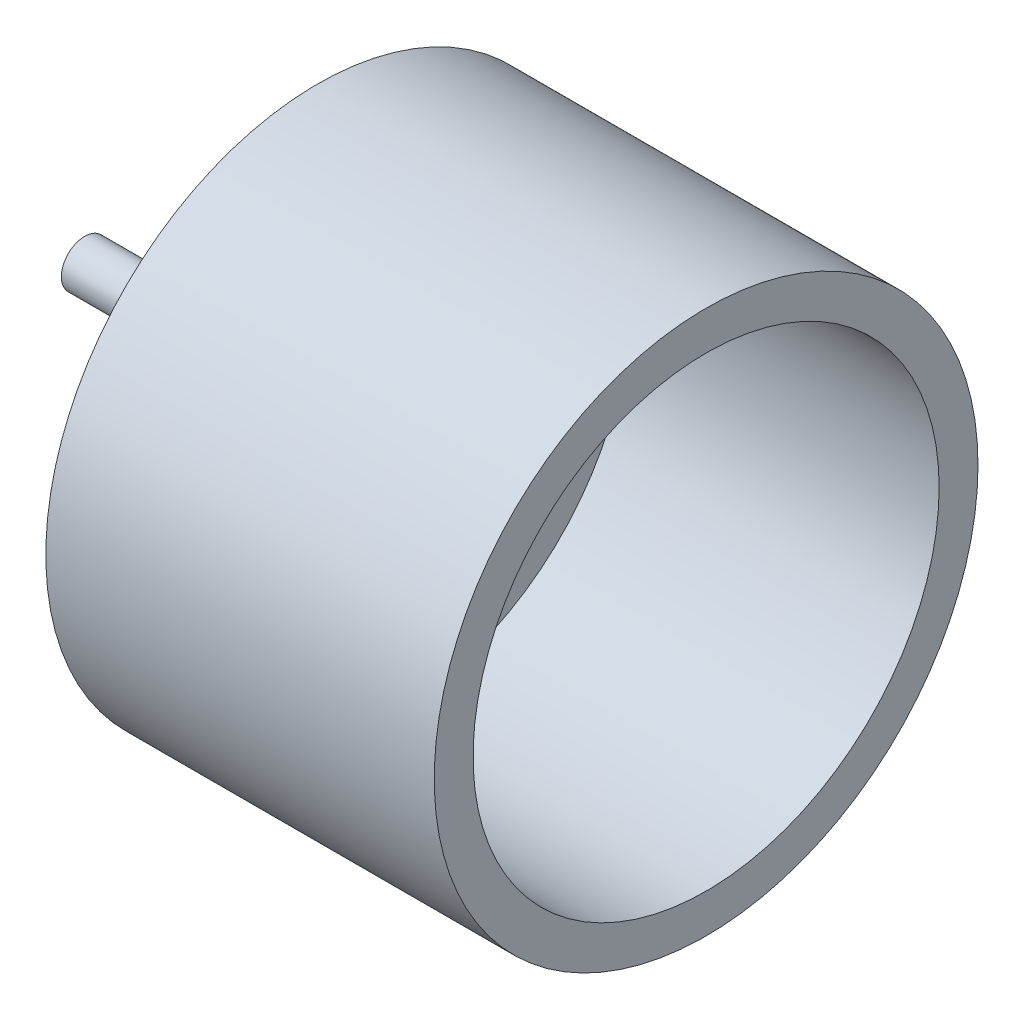
SolidWorks part; units mm, degrees
ref_plane "Front Plane" through (0, 0, 0) normal (0, 0, 1) x (1, 0, 0)
ref_plane "Top Plane" through (0, 0, 0) normal (0, 1, 0) x (1, 0, 0)
ref_plane "Right Plane" through (0, 0, 0) normal (1, 0, 0) x (0, 0, -1)
sketch "Sketch1" plane through (0, 0, 0) normal (1, 0, 0) x (0, 0, -1)
  circle A0 centre (0, 0) radius 17.5
  circle A1 centre (0, 0) radius 15
  circle A2 centre (0, 0) radius 1.5
  dimension "D1" = 35
  dimension "D2" = 3
  dimension "D3" = 30
extrude "Boss-Extrude1" add sketch "Sketch1" along normal blind 25 contours A0 A1 region at (0, 0, 17.005)
extrude "Boss-Extrude2" add sketch "Sketch1<3>" along normal blind 5 contours A1 A2 region at (0, 0, 14.5757)
sketch "Sketch1<3>" plane through (0, 0, 0) normal (1, 0, 0) x (0, 0, -1) same geometry as "Sketch1"
extrude "Boss-Extrude3" add sketch "Sketch1<4>" along normal blind 5 and the other way blind 15 contours A2 region at (0, 0, 0)
sketch "Sketch1<4>" plane through (0, 0, 0) normal (1, 0, 0) x (0, 0, -1) same geometry as "Sketch1"
